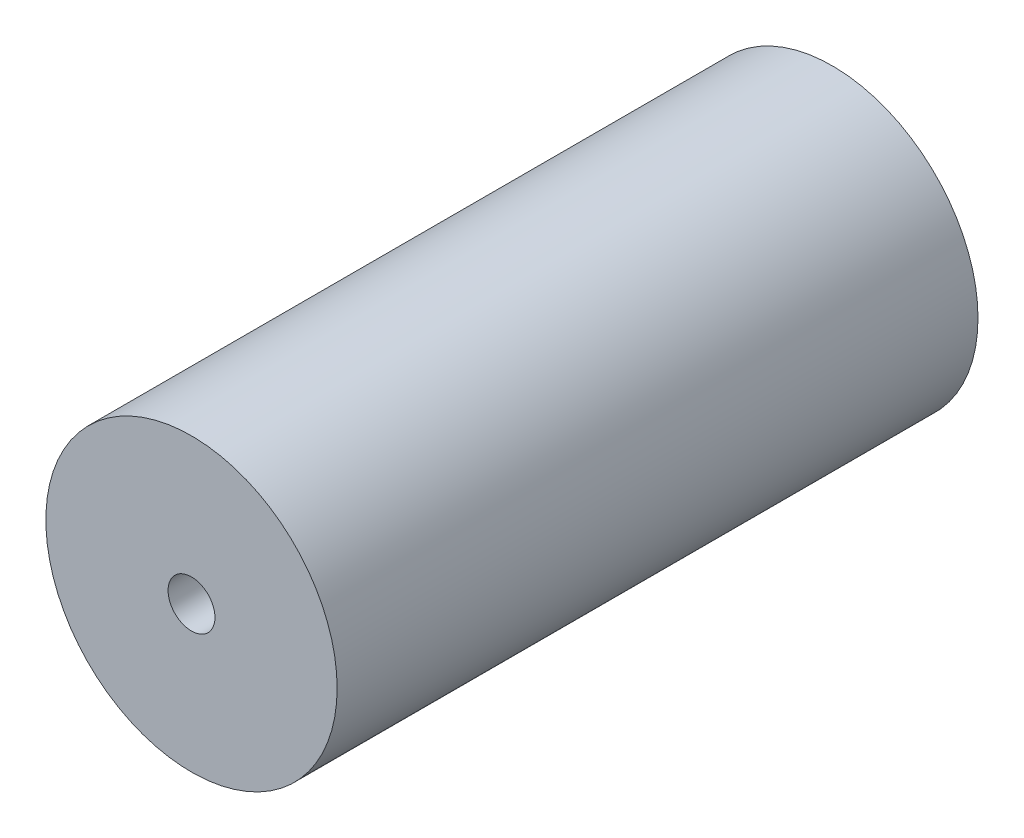
SolidWorks part; units mm, degrees
ref_plane "Ebene vorne" through (0, 0, 0) normal (0, 0, 1) x (1, 0, 0)
ref_plane "Ebene oben" through (0, 0, 0) normal (0, 1, 0) x (1, 0, 0)
ref_plane "Ebene rechts" through (0, 0, 0) normal (1, 0, 0) x (0, 0, -1)
sketch "Skizze1" plane through (0, 0, 0) normal (0, 0, 1) x (1, 0, 0)
  circle A0 centre (0, 0) radius 4.025
  circle A1 centre (0, 0) radius 25
  dimension "D1" = 8.05
  dimension "D2" = 50
extrude "Aufsatz-Linear austragen1" add sketch "Skizze1" along normal blind 110
